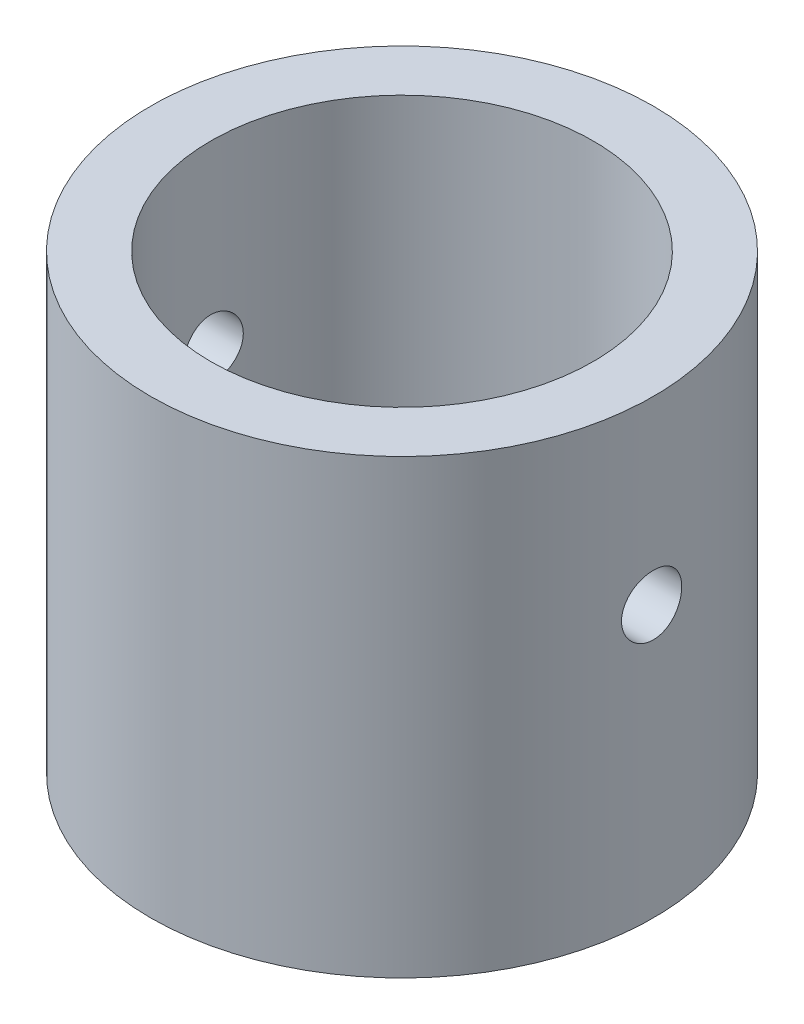
SolidWorks part; units mm, degrees
ref_plane "Front Plane" through (0, 0, 0) normal (0, 0, 1) x (1, 0, 0)
ref_plane "Top Plane" through (0, 0, 0) normal (0, 1, 0) x (1, 0, 0)
ref_plane "Right Plane" through (0, 0, 0) normal (1, 0, 0) x (0, 0, -1)
sketch "Sketch1" plane through (0, 0, 0) normal (0, 1, 0) x (1, 0, 0)
  circle A0 centre (0, 0) radius 6.35 construction
  circle A1 centre (0, 0) radius 8.35
  dimension "D1" = 12.7
  dimension "D2" = 2
extrude "Boss-Extrude1" add sketch "Sketch1" along normal blind 15
sketch "Sketch2" plane through (0, 15, 0) normal (0, 1, 0) x (1, 0, 0)
  circle A0 centre (0, 0) radius 6.35
  dimension "D1" = 12.7
extrude "Cut-Extrude1" cut sketch "Sketch2" against normal offset from surface (12 mm away) 3 up to face at (0, 0, 8.35)
sketch "Sketch3" plane through (0, 0, 0) normal (1, 0, 0) x (0, 0, -1)
  line L0 (0, 15) -> (0, 9) construction
  line L1 (6.35, 15) -> (-6.35, 15) construction
  circle A0 centre (0, 9) radius 1
  dimension "D2" = 2
  dimension "D1" = 6
extrude "Cut-Extrude2" cut sketch "Sketch3" against normal through all both and the other way through all
sketch "Sketch4" plane through (0, 0, 0) normal (0, -1, 0) x (1, 0, 0)
  circle A0 centre (0, 0) radius 4
  dimension "D1" = 8
extrude "Cut-Extrude3" cut sketch "Sketch4" against normal through all
